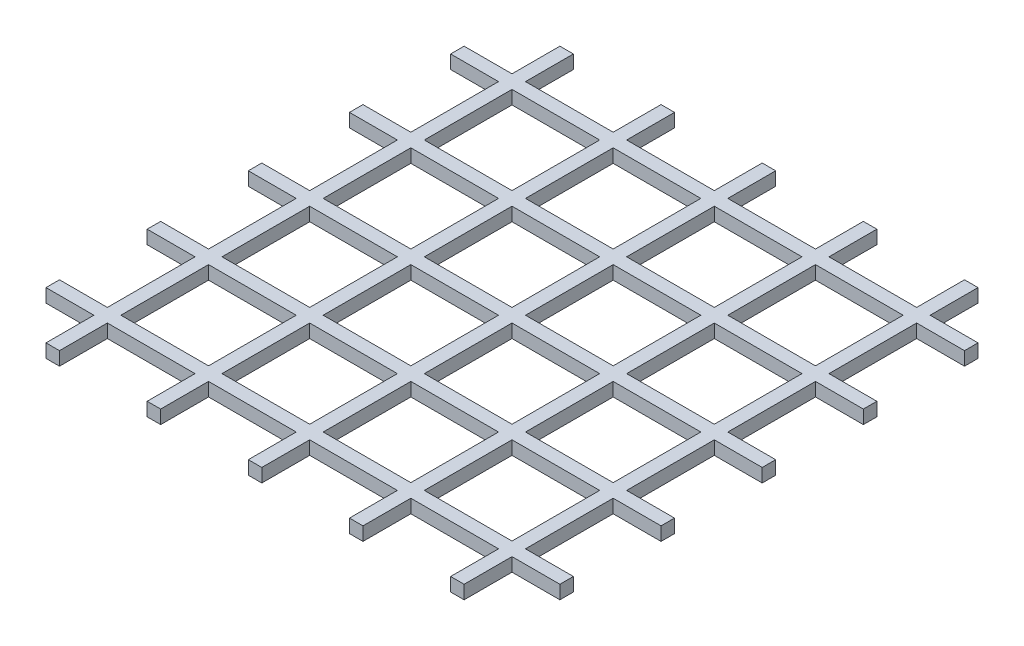
SolidWorks part; units mm, degrees
ref_plane "Front Plane" through (0, 0, 0) normal (0, 0, 1) x (1, 0, 0)
ref_plane "Top Plane" through (0, 0, 0) normal (0, 1, 0) x (1, 0, 0)
ref_plane "Right Plane" through (0, 0, 0) normal (1, 0, 0) x (0, 0, -1)
sketch "Sketch1" plane through (0, 0, 0) normal (0, 1, 0) x (1, 0, 0)
  line L0 (3.1333, 24.3333) -> (3.1333, -51.8667)
  line L1 (-13.8667, 24.3333) -> (-11.8667, 24.3333)
  line L2 (-13.8667, 24.3333) -> (-13.8667, -51.8667)
  line L3 (-13.8667, -51.8667) -> (-11.8667, -51.8667)
  line L4 (-11.8667, 24.3333) -> (-11.8667, -51.8667)
  line L5 (1.1333, 24.3333) -> (3.1333, 24.3333)
  line L6 (1.1333, 24.3333) -> (1.1333, -51.8667)
  line L7 (1.1333, -51.8667) -> (3.1333, -51.8667)
  line L8 (18.1333, 24.3333) -> (18.1333, -51.8667)
  line L9 (16.1333, 24.3333) -> (18.1333, 24.3333)
  line L10 (16.1333, 24.3333) -> (16.1333, -51.8667)
  line L11 (16.1333, -51.8667) -> (18.1333, -51.8667)
  line L12 (33.1333, 24.3333) -> (33.1333, -51.8667)
  line L13 (31.1333, 24.3333) -> (33.1333, 24.3333)
  line L14 (31.1333, 24.3333) -> (31.1333, -51.8667)
  line L15 (31.1333, -51.8667) -> (33.1333, -51.8667)
  line L16 (48.1333, 24.3333) -> (48.1333, -51.8667)
  line L17 (46.1333, 24.3333) -> (48.1333, 24.3333)
  line L18 (46.1333, 24.3333) -> (46.1333, -51.8667)
  line L19 (46.1333, -51.8667) -> (48.1333, -51.8667)
  dimension "D1" = 2
  dimension "D2" = 76.2
  dimension "D3" = 5
extrude "Boss-Extrude1" add sketch "Sketch1" along normal blind 2
sketch "Sketch2" plane through (0, 0, 0) normal (0, 1, 0) x (1, 0, 0)
  line L0 (-20.9667, 2.2333) -> (-20.9667, 0.2333)
  line L1 (-20.9667, 17.2333) -> (55.2333, 17.2333)
  line L2 (-20.9667, 17.2333) -> (-20.9667, 15.2333)
  line L3 (-20.9667, 15.2333) -> (55.2333, 15.2333)
  line L4 (55.2333, 17.2333) -> (55.2333, 15.2333)
  line L5 (-20.9667, 0.2333) -> (55.2333, 0.2333)
  line L6 (55.2333, 2.2333) -> (55.2333, 0.2333)
  line L7 (-20.9667, 2.2333) -> (55.2333, 2.2333)
  line L8 (-20.9667, -12.7667) -> (-20.9667, -14.7667)
  line L9 (-20.9667, -14.7667) -> (55.2333, -14.7667)
  line L10 (55.2333, -12.7667) -> (55.2333, -14.7667)
  line L11 (-20.9667, -12.7667) -> (55.2333, -12.7667)
  line L12 (-20.9667, -27.7667) -> (-20.9667, -29.7667)
  line L13 (-20.9667, -29.7667) -> (55.2333, -29.7667)
  line L14 (55.2333, -27.7667) -> (55.2333, -29.7667)
  line L15 (-20.9667, -27.7667) -> (55.2333, -27.7667)
  line L16 (-20.9667, -42.7667) -> (-20.9667, -44.7667)
  line L17 (-20.9667, -44.7667) -> (55.2333, -44.7667)
  line L18 (55.2333, -42.7667) -> (55.2333, -44.7667)
  line L19 (-20.9667, -42.7667) -> (55.2333, -42.7667)
  line L20 (-13.8667, 24.3333) -> (-13.8667, -51.8667) construction
  line L21 (48.1333, -51.8667) -> (48.1333, 24.3333) construction
  line L22 (-11.8667, 24.3333) -> (-13.8667, 24.3333) construction
  dimension "D1" = 76.2
  dimension "D3" = 7.1
  dimension "D4" = 7.1
  dimension "D5" = 7.1
  dimension "D6" = 2
  dimension "D2" = 5
extrude "Boss-Extrude2" add sketch "Sketch2" along normal blind 2
